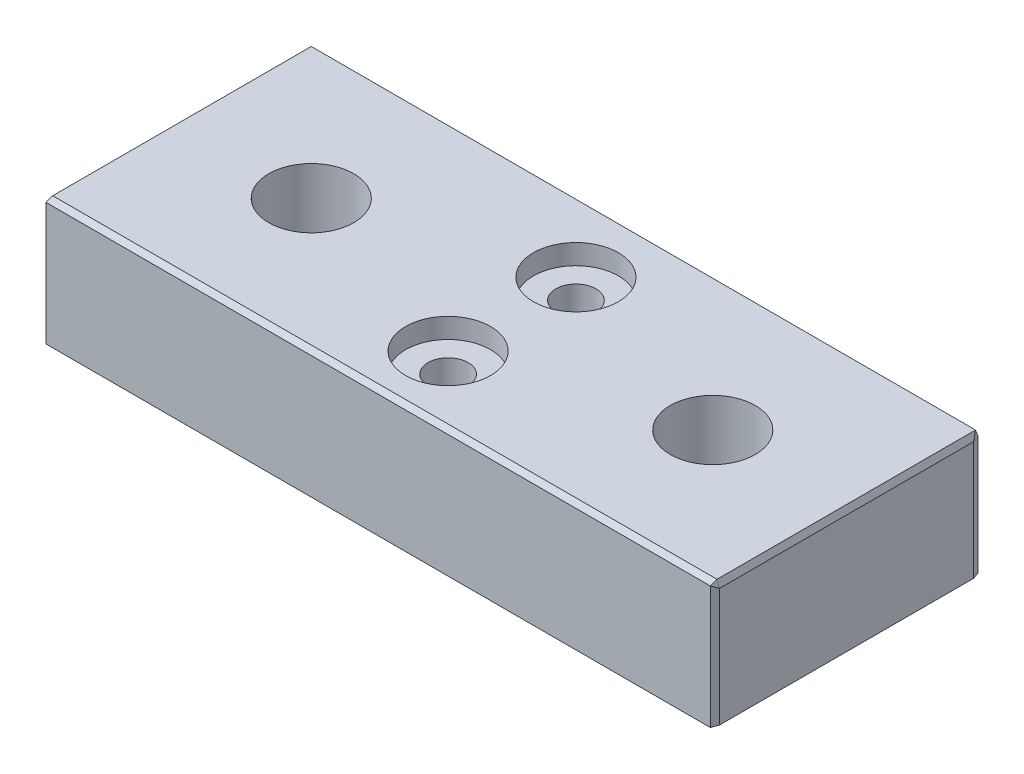
SolidWorks part; units mm, degrees
material "6061-T6 (SS)"
ref_plane "Front Plane" through (0, 0, 0) normal (0, 0, 1) x (1, 0, 0)
ref_plane "Top Plane" through (0, 0, 0) normal (0, 1, 0) x (1, 0, 0)
ref_plane "Right Plane" through (0, 0, 0) normal (1, 0, 0) x (0, 0, -1)
sketch "Sketch3" plane through (0, 0, 0) normal (0, 1, 0) x (1, 0, 0)
  line L1 (-50, 20) -> (50, 20)
  line L2 (-50, 20) -> (-50, -20)
  line L3 (-50, -20) -> (50, -20)
  line L4 (50, 20) -> (50, -20)
  line L5 (-50, 20) -> (50, -20) construction
  line L6 (-50, -20) -> (50, 20) construction
  point P0 (0, 0)
  dimension "D1" = 100
  dimension "D2" = 40
extrude "Boss-Extrude1" add sketch "Sketch3" along normal blind 19.05
sketch "Sketch4" plane through (0, 19.05, 0) normal (0, 1, 0) x (1, 0, 0)
  line L0 (-50, 0) -> (50, 0) construction
  line L1 (-50, 20) -> (-50, -20) construction
  line L2 (50, -20) -> (50, 20) construction
  line L3 (0, 20) -> (0, -20) construction
  line L4 (50, 20) -> (-50, 20) construction
  line L5 (-50, -20) -> (50, -20) construction
  circle A0 centre (0, 9.55) radius 3
  circle A1 centre (0, -9.55) radius 3
  circle A2 centre (-30, 0) radius 6.35
  circle A3 centre (30, 0) radius 6.35
  dimension "D1" = 6
  dimension "D4" = 60
  dimension "D6" = 12.7
  dimension "D2" = 19.1
  dimension "D3" = 9.55
  dimension "D5" = 30
extrude "Cut-Extrude1" cut sketch "Sketch4" against normal through all
sketch "Sketch5" plane through (0, 19.05, 0) normal (0, 1, 0) x (1, 0, 0)
  circle A0 centre (0, 9.55) radius 6.35
  circle A1 centre (0, -9.55) radius 6.35
  dimension "D1" = 12.7
extrude "Cut-Extrude2" cut sketch "Sketch5" against normal blind 3
chamfer "Chamfer1" distance 1 angle 20 12 edges at (0, 19.05, -20) (0, 0, -20) (50, 19.05, 0) (50, 9.525, -20) (50, 0, 0) (-50, 9.525, -20) (-50, 19.05, 0) (-50, 0, 0) (-50, 9.525, 20) (0, 19.05, 20) (50, 9.525, 20) (0, 0, 20)
